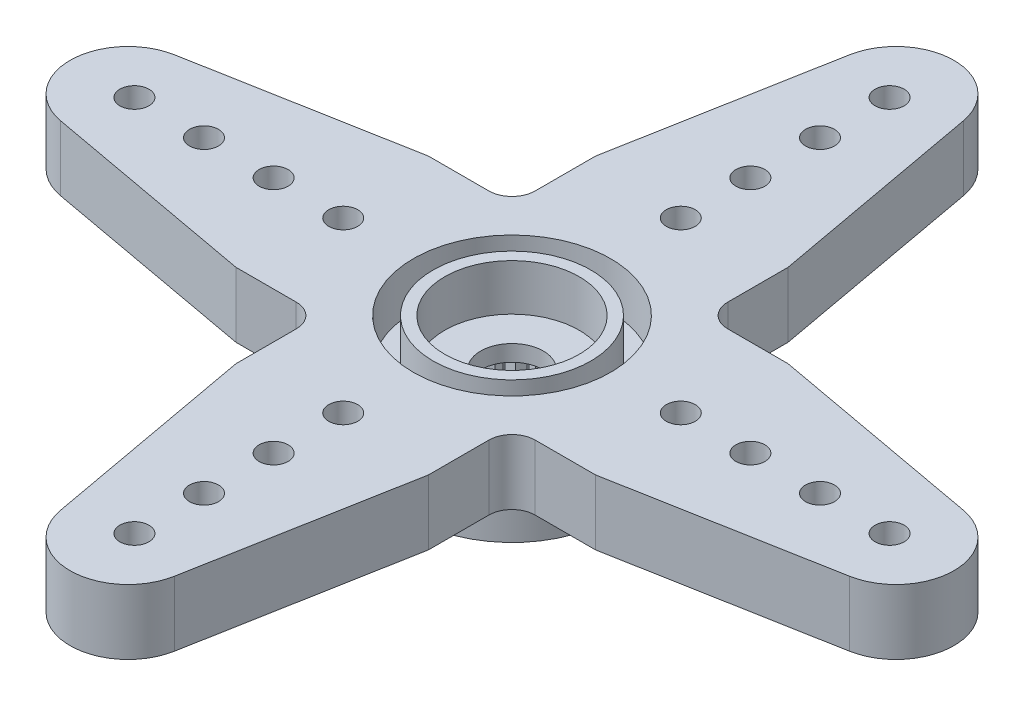
SolidWorks part; units mm, degrees
ref_plane "Front Plane" through (0, 0, 0) normal (0, 0, 1) x (1, 0, 0)
ref_plane "Top Plane" through (0, 0, 0) normal (0, 1, 0) x (1, 0, 0)
ref_plane "Right Plane" through (0, 0, 0) normal (1, 0, 0) x (0, 0, -1)
sketch "Sketch1" plane through (0, 0, 0) normal (0, 1, 0) x (1, 0, 0)
  circle A0 centre (0, 0) radius 4.35
  dimension "D1" = 8.7
extrude "Rebaixo de Encaixe" add sketch "Sketch1" along normal blind 2.6
sketch "Sketch14" plane through (0, 0, 0) normal (0, -1, 0) x (1, 0, 0)
  circle A0 centre (0, 0) radius 2.45
  dimension "D1" = 4.9
extrude "Furo de Encaixe - Servo" cut sketch "Sketch14" against normal blind 3
sketch "Sketch5" [suppressed] plane through (0, 2.6, 0) normal (0, 1, 0) x (1, 0, 0)
  circle A0 centre (0, 0) radius 1.35
  circle A1 centre (0, 0) radius 10.45
  dimension "D1" = 20.9
  dimension "D2" = 2.7
extrude "Base Redonda" [suppressed] add sketch "Sketch5" along normal blind 2
sketch "Sketch8" [suppressed] plane through (0, 4.6, 0) normal (0, 1, 0) x (1, 0, 0)
  circle A0 centre (0, 0) radius 3.425
  circle A1 centre (0, 0) radius 2.925
  dimension "D1" = 6.85
  dimension "D2" = 0.5
extrude "Ressalto" [suppressed] add sketch "Sketch8" along normal blind 0.8
sketch "Sketch9" [suppressed] plane through (0, 4.6, 0) normal (0, 1, 0) x (1, 0, 0)
  line L0 (0, 0) -> (0, 7.15) construction
  line L1 (-7.15, -7.15) -> (7.15, -7.15) construction
  line L2 (-7.15, -7.15) -> (-7.15, 7.15) construction
  line L3 (-7.15, 7.15) -> (7.15, 7.15) construction
  line L4 (7.15, -7.15) -> (7.15, 7.15) construction
  line L5 (-7.15, -7.15) -> (7.15, 7.15) construction
  line L6 (-7.15, 7.15) -> (7.15, -7.15) construction
  circle A0 centre (0, 7.15) radius 0.65
  circle A1 centre (3.5, 7.15) radius 0.65
  circle A2 centre (-3.5, 7.15) radius 0.65
  circle A3 centre (7.15, 3.5) radius 0.65
  circle A4 centre (7.15, 0) radius 0.65
  circle A5 centre (7.15, -3.5) radius 0.65
  circle A6 centre (3.5, -7.15) radius 0.65
  circle A7 centre (0, -7.15) radius 0.65
  circle A8 centre (-3.5, -7.15) radius 0.65
  circle A9 centre (-7.15, -3.5) radius 0.65
  circle A10 centre (-7.15, 0) radius 0.65
  circle A11 centre (-7.15, 3.5) radius 0.65
  point P0 (0, 0)
  point P6 (7.15, 0)
  point P35 (0, 0)
  dimension "D3" = 1.3
  dimension "D4" = 3.5
  dimension "D5" = 3.5
  dimension "D1" = 14.3
  dimension "D2" = 14.3
  dimension "D6" = 4
extrude "Furos de Fixação - Carga Redondo" [suppressed] cut sketch "Sketch9" against normal through all
sketch "Sketch10" [suppressed] plane through (0, 2.6, 0) normal (0, 1, 0) x (1, 0, 0)
  line L0 (0, 0) -> (25.65, 0) construction
  line L1 (26.1003, 3.8236) -> (0.8012, 6.803)
  line L2 (26.1003, -3.8236) -> (0.8012, -6.803)
  arc A0 (0.8012, 6.803) -> (0.8012, -6.803) centre (0, 0) ccw
  circle A1 centre (0, 0) radius 1.35
  arc A3 (26.1003, -3.8236) -> (26.1003, 3.8236) centre (25.65, 0) ccw
  dimension "D1" = 13.7
  dimension "D2" = 32.5
  dimension "D3" = 3.85
  dimension "D4" = 2.7
extrude "Base de 1 Braço" [suppressed] add sketch "Sketch10" along normal blind 4.3
sketch "Sketch11" [suppressed] plane through (0, 6.9, 0) normal (0, 1, 0) x (1, 0, 0)
  circle A0 centre (0, 0) radius 4.25
  dimension "D1" = 8.5
extrude "Rebaixo de Alojamento - 1 Braço" [suppressed] cut sketch "Sketch11" against normal blind 2.1 draft 25
sketch "Sketch12" [suppressed] plane through (0, 0, 0) normal (0, 0, 1) x (1, 0, 0)
  line L0 (29.5, 4.75) -> (11.5, 4.75) construction
  line L1 (29.5, 2.6) -> (29.5, 6.9) construction
  line L2 (11.5, 2.6) -> (11.5, 6.9) construction
  line L3 (0.8012, 2.6) -> (26.1003, 2.6) construction
  line L4 (0.8012, 6.9) -> (26.1003, 6.9) construction
  line L5 (29.5, 2.6) -> (29.5, 3.75)
  line L6 (29.5, 6.9) -> (11.5, 6.9)
  line L7 (29.5, 6.9) -> (29.5, 5.75)
  line L8 (29.5, 5.75) -> (11.5, 5.75)
  line L9 (11.5, 6.9) -> (11.5, 5.75)
  line L10 (29.5, 3.75) -> (11.5, 3.75)
  line L11 (29.5, 2.6) -> (11.5, 2.6)
  line L12 (11.5, 2.6) -> (11.5, 3.75)
  dimension "D1" = 18
  dimension "D2" = 1.15
extrude "Corte do Braço 1" [suppressed] cut sketch "Sketch12" against normal mid plane 13
chamfer "Chanfros 1mm - 1 Braço" [suppressed] distance 1 angle 45
sketch "Sketch15" [suppressed] plane through (0, 5.75, 0) normal (0, 1, 0) x (1, 0, 0)
  line L0 (29.5, 0) -> (11.5, 0) construction
  line L1 (11.5, 5.543) -> (11.5, -5.543) construction
  arc A0 (26.1003, -3.8236) -> (26.1003, 3.8236) centre (25.65, 0) ccw construction
  circle A1 centre (26.15, 0) radius 0.65
  circle A2 centre (23.15, 0) radius 0.65
  circle A3 centre (20.15, 0) radius 0.65
  circle A4 centre (17.15, 0) radius 0.65
  dimension "D1" = 3.35
  dimension "D2" = 1.3
  dimension "D4" = 3
  dimension "D3" = 4
extrude "Furos de Fixação - Carga 1 Braço" [suppressed] cut sketch "Sketch15" against normal through all
sketch "Sketch16" [suppressed] plane through (0, 0, 0) normal (0, -1, 0) x (1, 0, 0)
  circle A0 centre (0, 0) radius 4.35
  dimension "D1" = 8.7
extrude "Fix Altura Rebaixo - 1 Braço" [suppressed] cut sketch "Sketch16" against normal blind 0.8
sketch "Sketch17" [suppressed] plane through (0, 0.8, 0) normal (0, -1, 0) x (1, 0, 0)
  circle A0 centre (0, 0) radius 5
  dimension "D1" = 10
extrude "Fix Diam. Rebaixo - 1 Braço" [suppressed] add sketch "Sketch17" against normal up to next
sketch "Sketch19" [suppressed] plane through (0, 2.6, 0) normal (0, 1, 0) x (1, 0, 0)
  line L0 (23.85, 0) -> (-23.85, 0) construction
  line L1 (0, -6.9) -> (0, 6.9) construction
  line L2 (0.628, 6.8205) -> (24.3335, 3.8195)
  line L3 (-0.628, 6.8205) -> (-24.3335, 3.8195)
  line L4 (-0.628, -6.8205) -> (-24.3335, -3.8195)
  line L5 (0.628, -6.8205) -> (24.3335, -3.8195)
  arc A0 (-0.628, 6.8205) -> (0.628, 6.8205) centre (0, 1.8601) cw
  arc A1 (24.3335, -3.8195) -> (24.3335, 3.8195) centre (23.85, 0) ccw
  arc A2 (-24.3335, 3.8195) -> (-24.3335, -3.8195) centre (-23.85, 0) ccw
  arc A3 (-0.628, -6.8205) -> (0.628, -6.8205) centre (0, -1.8601) ccw
  circle A4 centre (0, 0) radius 1.35
  point P6 (0, 0)
  point P17 (0, 0)
  dimension "D1" = 7.7
  dimension "D4" = 5
  dimension "D5" = 2.7
  dimension "D2" = 13.8
  dimension "D3" = 27.7
extrude "Base 2 Braços" [suppressed] add sketch "Sketch19" along normal blind 4
sketch "Sketch22" [suppressed] plane through (0, 6.6, 0) normal (0, 1, 0) x (1, 0, 0)
  circle A0 centre (0, 0) radius 4.25
  dimension "D1" = 8.5
extrude "Rebaixo de Alojamento - 2 Braços" [suppressed] cut sketch "Sketch22" against normal blind 2 draft 25
sketch "Sketch20" [suppressed] plane through (0, 6.6, 0) normal (0, 1, 0) x (1, 0, 0)
  line L0 (27.7, 0) -> (-27.7, 0) construction
  line L1 (0, 6.8601) -> (0, -6.8601) construction
  arc A0 (24.3335, -3.8195) -> (24.3335, 3.8195) centre (23.85, 0) ccw construction
  arc A1 (-24.3335, 3.8195) -> (-24.3335, -3.8195) centre (-23.85, 0) ccw construction
  arc A2 (0.628, 6.8205) -> (-0.628, 6.8205) centre (0, 1.8601) ccw construction
  arc A3 (-0.628, -6.8205) -> (0.628, -6.8205) centre (0, -1.8601) ccw construction
  circle A4 centre (24.35, 0) radius 0.65
  circle A5 centre (21.35, 0) radius 0.65
  circle A6 centre (18.35, 0) radius 0.65
  circle A7 centre (15.35, 0) radius 0.65
  circle A8 centre (-24.35, 0) radius 0.65
  circle A9 centre (-21.35, 0) radius 0.65
  circle A10 centre (-18.35, 0) radius 0.65
  circle A11 centre (-15.35, 0) radius 0.65
  dimension "D1" = 3.35
  dimension "D2" = 1.3
  dimension "D4" = 3
  dimension "D3" = 4
extrude "Furos de Fixação - Carga 2 Braços" [suppressed] cut sketch "Sketch20" against normal through all
sketch "Sketch21" [suppressed] plane through (0, 0, 0) normal (0, 0, 1) x (1, 0, 0)
  line L0 (0, 6.6) -> (0, 2.6) construction
  line L1 (0.628, 6.6) -> (-0.628, 6.6) construction
  line L2 (-4.35, 2.6) -> (4.35, 2.6) construction
  line L3 (27.7, 4.6) -> (-27.7, 4.6) construction
  line L4 (27.7, 2.6) -> (27.7, 6.6) construction
  line L5 (-27.7, 6.6) -> (-27.7, 2.6) construction
  line L6 (27.7, 2.6) -> (27.7, 3.6)
  line L7 (27.7, 6.6) -> (8.7, 6.6)
  line L8 (27.7, 6.6) -> (27.7, 5.6)
  line L9 (27.7, 5.6) -> (8.7, 5.6)
  line L10 (8.7, 6.6) -> (8.7, 5.6)
  line L11 (27.7, 2.6) -> (8.7, 2.6)
  line L12 (8.7, 2.6) -> (8.7, 3.6)
  line L13 (27.7, 3.6) -> (8.7, 3.6)
  line L14 (-27.7, 3.6) -> (-8.7, 3.6)
  line L15 (-8.7, 2.6) -> (-8.7, 3.6)
  line L16 (-27.7, 2.6) -> (-8.7, 2.6)
  line L17 (-8.7, 6.6) -> (-8.7, 5.6)
  line L18 (-27.7, 5.6) -> (-8.7, 5.6)
  line L19 (-27.7, 6.6) -> (-27.7, 5.6)
  line L20 (-27.7, 6.6) -> (-8.7, 6.6)
  line L21 (-27.7, 2.6) -> (-27.7, 3.6)
  dimension "D1" = 19
  dimension "D2" = 1
extrude "Corte do Braço 2" [suppressed] cut sketch "Sketch21" against normal mid plane 13
chamfer "Chanfros 1mm - 2 Braços" [suppressed] distance 1 angle 45
chamfer "Chanfros 1x3 - 2 Braços Cima" [suppressed] distance 3 distance2 1
chamfer "Chanfros 1x3 - 2 Braços Baixo" [suppressed] distance 1 distance2 3
sketch "Sketch23" [suppressed] plane through (0, 0, 0) normal (0, -1, 0) x (1, 0, 0)
  circle A0 centre (0, 0) radius 4.35
  dimension "D1" = 8.7
extrude "Fix Altura Rebaixo - 2 Braços" [suppressed] cut sketch "Sketch23" against normal blind 0.6
sketch "Sketch24" [suppressed] plane through (0, 0.6, 0) normal (0, -1, 0) x (1, 0, 0)
  circle A0 centre (0, 0) radius 5.15
  dimension "D1" = 10.3
extrude "Fix Diam. Rebaixo - 2 Braços" [suppressed] add sketch "Sketch24" against normal up to next
sketch "Sketch25" plane through (0, 2.6, 0) normal (0, 1, 0) x (1, 0, 0)
  line L5 (0, 0) -> (16.55, 0) construction
  line L6 (5.15, 4.15) -> (7.75, 4.15)
  line L8 (5.15, -4.15) -> (7.75, -4.15)
  line L10 (16.9995, 2.4593) -> (7.75, 4.15)
  line L11 (16.9995, -2.4593) -> (7.75, -4.15)
  line L12 (-4.15, -5.15) -> (-4.15, -7.75)
  line L14 (4.15, -5.15) -> (4.15, -7.75)
  line L15 (2.4593, -16.9995) -> (4.15, -7.75)
  line L16 (-2.4593, -16.9995) -> (-4.15, -7.75)
  line L17 (0, 0) -> (0, -16.55) construction
  line L18 (-5.15, 4.15) -> (-7.75, 4.15)
  line L20 (-5.15, -4.15) -> (-7.75, -4.15)
  line L21 (-16.9995, -2.4593) -> (-7.75, -4.15)
  line L22 (-16.9995, 2.4593) -> (-7.75, 4.15)
  line L23 (0, 0) -> (-16.55, 0) construction
  line L24 (4.15, 5.15) -> (4.15, 7.75)
  line L26 (-4.15, 5.15) -> (-4.15, 7.75)
  line L27 (-2.4593, 16.9995) -> (-4.15, 7.75)
  line L28 (2.4593, 16.9995) -> (4.15, 7.75)
  line L29 (0, 0) -> (0, 16.55) construction
  arc A0 (16.9995, -2.4593) -> (16.9995, 2.4593) centre (16.55, 0) ccw
  arc A1 (-2.4593, -16.9995) -> (2.4593, -16.9995) centre (0, -16.55) ccw
  arc A2 (-16.9995, 2.4593) -> (-16.9995, -2.4593) centre (-16.55, 0) ccw
  arc A3 (2.4593, 16.9995) -> (-2.4593, 16.9995) centre (0, 16.55) ccw
  arc A4 (4.15, 5.15) -> (5.15, 4.15) centre (5.15, 5.15) ccw
  arc A5 (4.15, -5.15) -> (5.15, -4.15) centre (5.15, -5.15) cw
  arc A6 (-4.15, -5.15) -> (-5.15, -4.15) centre (-5.15, -5.15) ccw
  arc A7 (-4.15, 5.15) -> (-5.15, 4.15) centre (-5.15, 5.15) cw
  circle A8 centre (0, 0) radius 1.35
  point P3 (0, 0)
  point P35 (0, 0)
  dimension "D3" = 2.5
  dimension "D2" = 1
  dimension "D7" = 2.7
  dimension "D1" = 8.3
  dimension "D4" = 16.55
  dimension "D6" = 16.9995
  dimension "D5" = 4
extrude "Base 4 Braços" add sketch "Sketch25" along normal blind 2.8
sketch "Sketch26" plane through (0, 5.4, 0) normal (0, 1, 0) x (1, 0, 0)
  line L0 (0, 0) -> (19.05, 0) construction
  line L1 (0, 0) -> (0, -19.05) construction
  line L2 (0, 0) -> (-19.05, 0) construction
  line L3 (0, 0) -> (0, 19.05) construction
  arc A0 (16.9995, -2.4593) -> (16.9995, 2.4593) centre (16.55, 0) ccw construction
  circle A1 centre (16.275, 0) radius 0.625
  circle A2 centre (13.275, 0) radius 0.625
  circle A3 centre (10.275, 0) radius 0.625
  circle A4 centre (7.275, 0) radius 0.625
  circle A5 centre (0, -16.275) radius 0.625
  circle A6 centre (0, -13.275) radius 0.625
  circle A7 centre (0, -10.275) radius 0.625
  circle A8 centre (0, -7.275) radius 0.625
  circle A9 centre (-16.275, 0) radius 0.625
  circle A10 centre (-13.275, 0) radius 0.625
  circle A11 centre (-10.275, 0) radius 0.625
  circle A12 centre (-7.275, 0) radius 0.625
  circle A13 centre (0, 16.275) radius 0.625
  circle A14 centre (0, 13.275) radius 0.625
  circle A15 centre (0, 10.275) radius 0.625
  circle A16 centre (0, 7.275) radius 0.625
  point P44 (0, 0)
  dimension "D1" = 1.25
  dimension "D2" = 4
  dimension "D3" = 3
  dimension "2,15" = 2.15
  dimension "D4" = 4
extrude "Furos de Fixação - Carga 4 Braços" cut sketch "Sketch26" against normal through all
sketch "Sketch27" plane through (0, 5.4, 0) normal (0, 1, 0) x (1, 0, 0)
  circle A0 centre (0, 0) radius 4.25
  circle A1 centre (0, 0) radius 2.9
  circle A2 centre (0, 0) radius 3.4
  circle M43 centre (0, 0) radius 1.35
  dimension "D1" = 8.5
  dimension "D2" = 5.8
  dimension "D3" = 0.5
extrude "Rebaixo Central - 4 Braços" cut sketch "Sketch27" against normal blind 2 contours A0 A2 | A1 M43 region at (-4.1298, 5.4, 0) region at (-2.818, 5.4, 0)
sketch "Sketch28" [suppressed] plane through (0, 2.6, 0) normal (0, -1, 0) x (-1, 0, 0)
  line L0 (9.0172, -10.6873) -> (6.8334, -4.8358)
  line L5 (0, 0) -> (13.35, 0) construction
  line L10 (13.7641, 2.4655) -> (7.6047, 3.5)
  line L11 (13.7641, -2.4655) -> (7.6047, -3.5)
  line L12 (4.7469, -13.1528) -> (0.7712, -8.3358)
  line L13 (0, 0) -> (6.675, -11.5614) construction
  line L14 (-4.7469, -13.1528) -> (-0.7712, -8.3358)
  line L15 (-9.0172, -10.6873) -> (-6.8334, -4.8358)
  line L16 (0, 0) -> (-6.675, -11.5614) construction
  line L17 (-13.7641, -2.4655) -> (-7.6047, -3.5)
  line L18 (-13.7641, 2.4655) -> (-7.6047, 3.5)
  line L19 (0, 0) -> (-13.35, 0) construction
  line L20 (-9.0172, 10.6873) -> (-6.8334, 4.8358)
  line L21 (-4.7469, 13.1528) -> (-0.7712, 8.3358)
  line L22 (0, 0) -> (-6.675, 11.5614) construction
  line L23 (4.7469, 13.1528) -> (0.7712, 8.3358)
  line L24 (9.0172, 10.6873) -> (6.8334, 4.8358)
  line L25 (0, 0) -> (6.675, 11.5614) construction
  arc A0 (13.7641, -2.4655) -> (13.7641, 2.4655) centre (13.35, 0) ccw
  circle A9 centre (0, 0) radius 7.5 construction
  arc A10 (4.7469, -13.1528) -> (9.0172, -10.6873) centre (6.675, -11.5614) ccw
  arc A11 (-9.0172, -10.6873) -> (-4.7469, -13.1528) centre (-6.675, -11.5614) ccw
  arc A12 (-13.7641, 2.4655) -> (-13.7641, -2.4655) centre (-13.35, 0) ccw
  arc A13 (-4.7469, 13.1528) -> (-9.0172, 10.6873) centre (-6.675, 11.5614) ccw
  arc A14 (9.0172, 10.6873) -> (4.7469, 13.1528) centre (6.675, 11.5614) ccw
  arc A15 (6.8334, 4.8358) -> (7.6047, 3.5) centre (7.7703, 4.4862) ccw
  arc A16 (7.6047, -3.5) -> (6.8334, -4.8358) centre (7.7703, -4.4862) ccw
  arc A17 (0.7712, -8.3358) -> (-0.7712, -8.3358) centre (0, -8.9724) ccw
  arc A18 (-6.8334, -4.8358) -> (-7.6047, -3.5) centre (-7.7703, -4.4862) ccw
  arc A19 (-7.6047, 3.5) -> (-6.8334, 4.8358) centre (-7.7703, 4.4862) ccw
  arc A20 (-0.7712, 8.3358) -> (0.7712, 8.3358) centre (0, 8.9724) ccw
  circle A21 centre (0, 0) radius 1.35
  point P36 (0, 0)
  dimension "D3" = 2.5
  dimension "D2" = 15
  dimension "D7" = 7
  dimension "D4" = 1
  dimension "D6" = 1
  dimension "D8" = 2.7
  dimension "D1" = 13.35
  dimension "D5" = 6
extrude "Base 6 Braços" [suppressed] add sketch "Sketch28" against normal blind 2.8
sketch "Sketch29" [suppressed] plane through (0, 5.4, 0) normal (0, 1, 0) x (1, 0, 0)
  line L0 (0, 0) -> (15.85, 0) construction
  line L1 (0, 0) -> (7.925, -13.7265) construction
  line L2 (0, 0) -> (-7.925, -13.7265) construction
  line L3 (0, 0) -> (-15.85, 0) construction
  line L4 (0, 0) -> (-7.925, 13.7265) construction
  line L5 (0, 0) -> (7.925, 13.7265) construction
  arc A0 (13.7641, -2.4655) -> (13.7641, 2.4655) centre (13.35, 0) ccw construction
  circle A1 centre (13.7, 0) radius 0.625
  circle A2 centre (10.7, 0) radius 0.625
  circle A3 centre (7.7, 0) radius 0.625
  circle A4 centre (6.85, -11.8645) radius 0.625
  circle A5 centre (5.35, -9.2665) radius 0.625
  circle A6 centre (3.85, -6.6684) radius 0.625
  circle A7 centre (-6.85, -11.8645) radius 0.625
  circle A8 centre (-5.35, -9.2665) radius 0.625
  circle A9 centre (-3.85, -6.6684) radius 0.625
  circle A10 centre (-13.7, 0) radius 0.625
  circle A11 centre (-10.7, 0) radius 0.625
  circle A12 centre (-7.7, 0) radius 0.625
  circle A13 centre (-6.85, 11.8645) radius 0.625
  circle A14 centre (-5.35, 9.2665) radius 0.625
  circle A15 centre (-3.85, 6.6684) radius 0.625
  circle A16 centre (6.85, 11.8645) radius 0.625
  circle A17 centre (5.35, 9.2665) radius 0.625
  circle A18 centre (3.85, 6.6684) radius 0.625
  point P49 (0, 0)
  dimension "D1" = 2.15
  dimension "D2" = 1.25
  dimension "D4" = 3
  dimension "D3" = 3
extrude "Furos de Fixação - Carga 6 Braços" [suppressed] cut sketch "Sketch29" against normal through all
sketch "Sketch30" [suppressed] plane through (0, 5.4, 0) normal (0, 1, 0) x (1, 0, 0)
  circle A0 centre (0, 0) radius 4.25
  circle A1 centre (0, 0) radius 2.9
  circle A2 centre (0, 0) radius 3.4
  circle M21 centre (0, 0) radius 1.35
  dimension "D1" = 8.5
  dimension "D2" = 5.8
  dimension "D3" = 0.5
extrude "Cut-Extrude2" [suppressed] cut sketch "Sketch30" against normal blind 2 contours A1 M21 | A0 A2
sketch "Sketch31" plane through (0, 0, 0) normal (0, -1, 0) x (1, 0, 0)
  line L50 (-1.6931, -1.8394) -> (-1.7174, -2.3677)
  line L51 (-2.2177, -1.9072) -> (-1.6931, -1.8394)
  line L52 (-2.0974, -1.3605) -> (-2.2523, -1.8663)
  line L53 (-2.6223, -1.2958) -> (-2.0974, -1.3605)
  line L54 (-2.3698, -0.7962) -> (-2.6456, -1.2475)
  line L55 (-2.8622, -0.603) -> (-2.3698, -0.7962)
  line L56 (-2.4934, -0.1818) -> (-2.8728, -0.5504)
  line L57 (-2.9222, 0.1278) -> (-2.4934, -0.1818)
  line L58 (-2.4603, 0.444) -> (-2.9194, 0.1813)
  line L59 (-2.7986, 0.8505) -> (-2.4603, 0.444)
  line L60 (-2.2726, 1.0419) -> (-2.7826, 0.9017)
  line L61 (-2.4992, 1.5198) -> (-2.2726, 1.0419)
  line L62 (-1.9421, 1.5743) -> (-2.4709, 1.5653)
  line L63 (-2.0427, 2.0935) -> (-1.9421, 1.5743)
  line L64 (-1.4895, 2.0078) -> (-2.004, 2.1306)
  line L65 (-1.4579, 2.5358) -> (-1.4895, 2.0078)
  line L66 (-0.9434, 2.3152) -> (-1.4112, 2.5621)
  line L67 (-0.7815, 2.8187) -> (-0.9434, 2.3152)
  line L68 (-0.338, 2.477) -> (-0.7297, 2.8325)
  line L69 (-0.056, 2.9245) -> (-0.338, 2.477)
  line L70 (0.2886, 2.4833) -> (-0.0023, 2.925)
  line L71 (0.6731, 2.8465) -> (0.2886, 2.4833)
  line L72 (0.8971, 2.3335) -> (0.7252, 2.8337)
  line L73 (1.3598, 2.5897) -> (0.8971, 2.3335)
  line L74 (1.4492, 2.0371) -> (1.4071, 2.5643)
  line L75 (1.9611, 2.1701) -> (1.4492, 2.0371)
  line L76 (1.9103, 1.6127) -> (2.0006, 2.1338)
  line L77 (2.4392, 1.6142) -> (1.9103, 1.6127)
  line L78 (2.2514, 1.0869) -> (2.4684, 1.5693)
  line L79 (2.764, 0.9569) -> (2.2514, 1.0869)
  line L80 (2.4509, 0.4929) -> (2.7811, 0.9061)
  line L81 (2.9152, 0.2395) -> (2.4509, 0.4929)
  line L82 (2.4965, -0.1321) -> (2.9191, 0.186)
  line L83 (2.8831, -0.493) -> (2.4965, -0.1321)
  line L84 (2.3852, -0.7488) -> (2.8736, -0.5458)
  line L85 (2.67, -1.1946) -> (2.3852, -0.7488)
  line L86 (2.1241, -1.3185) -> (2.6476, -1.2433)
  line L87 (2.289, -1.821) -> (2.1241, -1.3185)
  line L88 (1.7294, -1.8053) -> (2.2552, -1.8627)
  line L89 (1.7642, -2.3331) -> (1.7294, -1.8053)
  line L90 (1.2261, -2.1787) -> (1.7212, -2.365)
  line L91 (1.1286, -2.6985) -> (1.2261, -2.1787)
  line L92 (0.6458, -2.4151) -> (1.0789, -2.7187)
  line L93 (0.422, -2.8944) -> (0.6458, -2.4151)
  line L94 (0.0249, -2.4999) -> (0.3689, -2.9016)
  line L95 (-0.311, -2.9084) -> (0.0249, -2.4999)
  line L96 (-0.5976, -2.4275) -> (-0.3643, -2.9022)
  line L97 (-1.0245, -2.7397) -> (-0.5976, -2.4275)
  line L98 (-1.1825, -2.2027) -> (-1.0746, -2.7205)
  line L99 (-1.6737, -2.3988) -> (-1.1825, -2.2027)
  line L100 (-1.6931, -1.8394) -> (-1.7174, -2.3677)
  line L101 (-2.2177, -1.9072) -> (-1.6931, -1.8394)
  line L102 (-2.0974, -1.3605) -> (-2.2523, -1.8663)
  line L103 (-2.6223, -1.2958) -> (-2.0974, -1.3605)
  line L104 (-2.3698, -0.7962) -> (-2.6456, -1.2475)
  line L105 (-2.8622, -0.603) -> (-2.3698, -0.7962)
  line L106 (-2.4934, -0.1818) -> (-2.8728, -0.5504)
  line L107 (-2.9222, 0.1278) -> (-2.4934, -0.1818)
  line L108 (-2.4603, 0.444) -> (-2.9194, 0.1813)
  line L109 (-2.7986, 0.8505) -> (-2.4603, 0.444)
  line L110 (-2.2726, 1.0419) -> (-2.7826, 0.9017)
  line L111 (-2.4992, 1.5198) -> (-2.2726, 1.0419)
  line L112 (-1.9421, 1.5743) -> (-2.4709, 1.5653)
  line L113 (-2.0427, 2.0935) -> (-1.9421, 1.5743)
  line L114 (-1.4895, 2.0078) -> (-2.004, 2.1306)
  line L115 (-1.4579, 2.5358) -> (-1.4895, 2.0078)
  line L116 (-0.9434, 2.3152) -> (-1.4112, 2.5621)
  line L117 (-0.7815, 2.8187) -> (-0.9434, 2.3152)
  line L118 (-0.338, 2.477) -> (-0.7297, 2.8325)
  line L119 (-0.056, 2.9245) -> (-0.338, 2.477)
  line L120 (0.2886, 2.4833) -> (-0.0023, 2.925)
  line L121 (0.6731, 2.8465) -> (0.2886, 2.4833)
  line L122 (0.8971, 2.3335) -> (0.7252, 2.8337)
  line L123 (1.3598, 2.5897) -> (0.8971, 2.3335)
  line L124 (1.4492, 2.0371) -> (1.4071, 2.5643)
  line L125 (1.9611, 2.1701) -> (1.4492, 2.0371)
  line L126 (1.9103, 1.6127) -> (2.0006, 2.1338)
  line L127 (2.4392, 1.6142) -> (1.9103, 1.6127)
  line L128 (2.2514, 1.0869) -> (2.4684, 1.5693)
  line L129 (2.764, 0.9569) -> (2.2514, 1.0869)
  line L130 (2.4509, 0.4929) -> (2.7811, 0.9061)
  line L131 (2.9152, 0.2395) -> (2.4509, 0.4929)
  line L132 (2.4965, -0.1321) -> (2.9191, 0.186)
  line L133 (2.8831, -0.493) -> (2.4965, -0.1321)
  line L134 (2.3852, -0.7488) -> (2.8736, -0.5458)
  line L135 (2.67, -1.1946) -> (2.3852, -0.7488)
  line L136 (2.1241, -1.3185) -> (2.6476, -1.2433)
  line L137 (2.289, -1.821) -> (2.1241, -1.3185)
  line L138 (1.7294, -1.8053) -> (2.2552, -1.8627)
  line L139 (1.7642, -2.3331) -> (1.7294, -1.8053)
  line L140 (1.2261, -2.1787) -> (1.7212, -2.365)
  line L141 (1.1286, -2.6985) -> (1.2261, -2.1787)
  line L142 (0.6458, -2.4151) -> (1.0789, -2.7187)
  line L143 (0.422, -2.8944) -> (0.6458, -2.4151)
  line L144 (0.0249, -2.4999) -> (0.3689, -2.9016)
  line L145 (-0.311, -2.9084) -> (0.0249, -2.4999)
  line L146 (-0.5976, -2.4275) -> (-0.3643, -2.9022)
  line L147 (-1.0245, -2.7397) -> (-0.5976, -2.4275)
  line L148 (-1.1825, -2.2027) -> (-1.0746, -2.7205)
  line L149 (-1.6737, -2.3988) -> (-1.1825, -2.2027)
  arc A25 (-1.7174, -2.3677) -> (-1.6737, -2.3988) centre (0, 0) ccw
  arc A26 (-2.2523, -1.8663) -> (-2.2177, -1.9072) centre (0, 0) ccw
  arc A27 (-2.6456, -1.2475) -> (-2.6223, -1.2958) centre (0, 0) ccw
  arc A28 (-2.8728, -0.5504) -> (-2.8622, -0.603) centre (0, 0) ccw
  arc A29 (-2.9194, 0.1813) -> (-2.9222, 0.1278) centre (0, 0) ccw
  arc A30 (-2.7826, 0.9017) -> (-2.7986, 0.8505) centre (0, 0) ccw
  arc A31 (-2.4709, 1.5653) -> (-2.4992, 1.5198) centre (0, 0) ccw
  arc A32 (-2.004, 2.1306) -> (-2.0427, 2.0935) centre (0, 0) ccw
  arc A33 (-1.4112, 2.5621) -> (-1.4579, 2.5358) centre (0, 0) ccw
  arc A34 (-0.7297, 2.8325) -> (-0.7815, 2.8187) centre (0, 0) ccw
  arc A35 (-0.0023, 2.925) -> (-0.056, 2.9245) centre (0, 0) ccw
  arc A36 (0.7252, 2.8337) -> (0.6731, 2.8465) centre (0, 0) ccw
  arc A37 (1.4071, 2.5643) -> (1.3598, 2.5897) centre (0, 0) ccw
  arc A38 (2.0006, 2.1338) -> (1.9611, 2.1701) centre (0, 0) ccw
  arc A39 (2.4684, 1.5693) -> (2.4392, 1.6142) centre (0, 0) ccw
  arc A40 (2.7811, 0.9061) -> (2.764, 0.9569) centre (0, 0) ccw
  arc A41 (2.9191, 0.186) -> (2.9152, 0.2395) centre (0, 0) ccw
  arc A42 (2.8736, -0.5458) -> (2.8831, -0.493) centre (0, 0) ccw
  arc A43 (2.6476, -1.2433) -> (2.67, -1.1946) centre (0, 0) ccw
  arc A44 (2.2552, -1.8627) -> (2.289, -1.821) centre (0, 0) ccw
  arc A45 (1.7212, -2.365) -> (1.7642, -2.3331) centre (0, 0) ccw
  arc A46 (1.0789, -2.7187) -> (1.1286, -2.6985) centre (0, 0) ccw
  arc A47 (0.3689, -2.9016) -> (0.422, -2.8944) centre (0, 0) ccw
  arc A48 (-0.3643, -2.9022) -> (-0.311, -2.9084) centre (0, 0) ccw
  arc A49 (-1.0746, -2.7205) -> (-1.0245, -2.7397) centre (0, 0) ccw
  arc A50 (-1.7174, -2.3677) -> (-1.6737, -2.3988) centre (0, 0) ccw
  arc A51 (-2.2523, -1.8663) -> (-2.2177, -1.9072) centre (0, 0) ccw
  arc A52 (-2.6456, -1.2475) -> (-2.6223, -1.2958) centre (0, 0) ccw
  arc A53 (-2.8728, -0.5504) -> (-2.8622, -0.603) centre (0, 0) ccw
  arc A54 (-2.9194, 0.1813) -> (-2.9222, 0.1278) centre (0, 0) ccw
  arc A55 (-2.7826, 0.9017) -> (-2.7986, 0.8505) centre (0, 0) ccw
  arc A56 (-2.4709, 1.5653) -> (-2.4992, 1.5198) centre (0, 0) ccw
  arc A57 (-2.004, 2.1306) -> (-2.0427, 2.0935) centre (0, 0) ccw
  arc A58 (-1.4112, 2.5621) -> (-1.4579, 2.5358) centre (0, 0) ccw
  arc A59 (-0.7297, 2.8325) -> (-0.7815, 2.8187) centre (0, 0) ccw
  arc A60 (-0.0023, 2.925) -> (-0.056, 2.9245) centre (0, 0) ccw
  arc A61 (0.7252, 2.8337) -> (0.6731, 2.8465) centre (0, 0) ccw
  arc A62 (1.4071, 2.5643) -> (1.3598, 2.5897) centre (0, 0) ccw
  arc A63 (2.0006, 2.1338) -> (1.9611, 2.1701) centre (0, 0) ccw
  arc A64 (2.4684, 1.5693) -> (2.4392, 1.6142) centre (0, 0) ccw
  arc A65 (2.7811, 0.9061) -> (2.764, 0.9569) centre (0, 0) ccw
  arc A66 (2.9191, 0.186) -> (2.9152, 0.2395) centre (0, 0) ccw
  arc A67 (2.8736, -0.5458) -> (2.8831, -0.493) centre (0, 0) ccw
  arc A68 (2.6476, -1.2433) -> (2.67, -1.1946) centre (0, 0) ccw
  arc A69 (2.2552, -1.8627) -> (2.289, -1.821) centre (0, 0) ccw
  arc A70 (1.7212, -2.365) -> (1.7642, -2.3331) centre (0, 0) ccw
  arc A71 (1.0789, -2.7187) -> (1.1286, -2.6985) centre (0, 0) ccw
  arc A72 (0.3689, -2.9016) -> (0.422, -2.8944) centre (0, 0) ccw
  arc A73 (-0.3643, -2.9022) -> (-0.311, -2.9084) centre (0, 0) ccw
  arc A74 (-1.0746, -2.7205) -> (-1.0245, -2.7397) centre (0, 0) ccw
  dimension "D1" = 0
extrude "Cut-Extrude3" cut sketch "Sketch31" against normal blind 2.7
